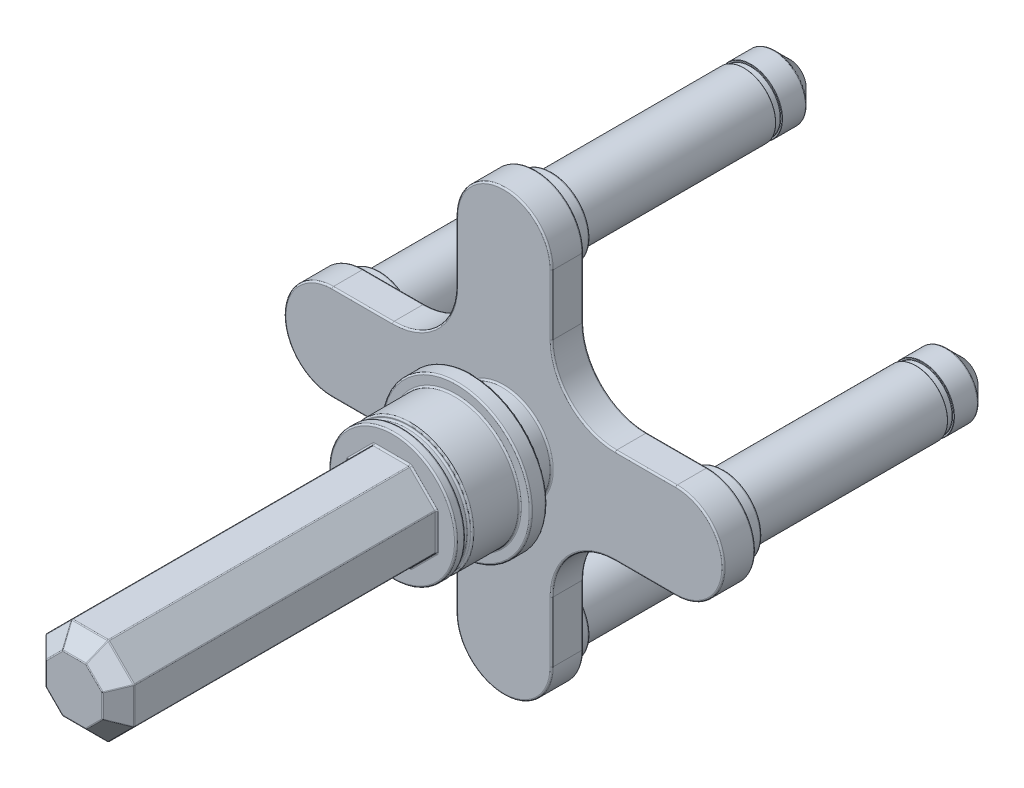
SolidWorks part; units mm, degrees
ref_plane "Front Plane" through (0, 0, 0) normal (0, 0, 1) x (1, 0, 0)
ref_plane "Top Plane" through (0, 0, 0) normal (0, 1, 0) x (1, 0, 0)
ref_plane "Right Plane" through (0, 0, 0) normal (1, 0, 0) x (0, 0, -1)
sketch "Sketch1" plane through (0, 0, 0) normal (0, 0, 1) x (1, 0, 0)
  line L2 (-7.5, 17.5) -> (-7.5, 27)
  line L3 (7.5, 17.5) -> (7.5, 27)
  line L4 (17.5, 7.5) -> (27, 7.5)
  line L5 (17.5, -7.5) -> (27, -7.5)
  line L7 (7.5, -17.5) -> (7.5, -27)
  line L8 (-7.5, -17.5) -> (-7.5, -27)
  line L10 (-17.5, -7.5) -> (-27, -7.5)
  line L11 (-17.5, 7.5) -> (-27, 7.5)
  arc A1 (7.5, 27) -> (-7.5, 27) centre (0, 27) ccw
  circle A2 centre (0, 27) radius 5
  circle A3 centre (27, 0) radius 5
  arc A5 (27, -7.5) -> (27, 7.5) centre (27, 0) ccw
  circle A6 centre (0, -27) radius 5
  arc A8 (-7.5, -27) -> (7.5, -27) centre (0, -27) ccw
  circle A9 centre (-27, 0) radius 5
  arc A11 (-27, 7.5) -> (-27, -7.5) centre (-27, 0) ccw
  arc A12 (7.5, -17.5) -> (17.5, -7.5) centre (17.5, -17.5) cw
  arc A13 (-7.5, -17.5) -> (-17.5, -7.5) centre (-17.5, -17.5) ccw
  arc A14 (7.5, 17.5) -> (17.5, 7.5) centre (17.5, 17.5) ccw
  arc A15 (-7.5, 17.5) -> (-17.5, 7.5) centre (-17.5, 17.5) cw
  point P12 (-13.5, 0)
  point P46 (0, -13.5)
  dimension "D1" = 7.5
  dimension "D2" = 10
  dimension "D4" = 10
  dimension "D5" = 27
extrude "Boss-Extrude1" add sketch "Sketch1" along normal blind 5 contours L2 A15 L11 A11 L10 A13 L8 A8 L7 A12 L5 A5 L4 A14 L3 A1 A2 A3 A6 A9 | A9 | A2 | A3 | A6 region at (0, 0, 0) region at (0, 27, 0) region at (27, 0, 0) region at (0, -27, 0) region at (-27, 0, 0)
sketch "Sketch2" plane through (0, 0, 0) normal (0, 0, -1) x (-1, 0, 0)
  line L0 (7.5, 17.5) -> (7.5, 27) construction
  line L1 (-17.5, -7.5) -> (-27, -7.5) construction
  line L8 (17.5, -7.5) -> (27, -7.5)
  line L9 (7.5, -27) -> (7.5, -17.5)
  line L10 (-7.5, -17.5) -> (-7.5, -27)
  line L11 (-27, -7.5) -> (-17.5, -7.5)
  line L12 (-17.5, 7.5) -> (-27, 7.5)
  line L13 (-7.5, 27) -> (-7.5, 17.5)
  line L14 (7.5, 17.5) -> (7.5, 27)
  line L15 (27, 7.5) -> (17.5, 7.5)
  line L16 (17.5, -7.5) -> (27, -7.5)
  line L17 (7.5, -27) -> (7.5, -17.5)
  line L18 (-7.5, -17.5) -> (-7.5, -27)
  line L19 (-27, -7.5) -> (-17.5, -7.5)
  line L20 (-17.5, 7.5) -> (-27, 7.5)
  line L21 (-7.5, 27) -> (-7.5, 17.5)
  line L22 (7.5, 17.5) -> (7.5, 27)
  line L23 (27, 7.5) -> (17.5, 7.5)
  circle A2 centre (-27, 0) radius 4.975
  circle A4 centre (0, 27) radius 4.975
  circle A6 centre (27, 0) radius 4.975
  circle A8 centre (0, -27) radius 4.975
  arc A16 (17.5, -7.5) -> (7.5, -17.5) centre (17.5, -17.5) ccw
  arc A17 (-7.5, -27) -> (7.5, -27) centre (0, -27) ccw
  arc A18 (-7.5, -17.5) -> (-17.5, -7.5) centre (-17.5, -17.5) ccw
  arc A19 (-27, 7.5) -> (-27, -7.5) centre (-27, 0) ccw
  arc A20 (-17.5, 7.5) -> (-7.5, 17.5) centre (-17.5, 17.5) ccw
  arc A21 (7.5, 27) -> (-7.5, 27) centre (0, 27) ccw
  arc A22 (7.5, 17.5) -> (17.5, 7.5) centre (17.5, 17.5) ccw
  arc A23 (27, -7.5) -> (27, 7.5) centre (27, 0) ccw
  arc A24 (17.5, -7.5) -> (7.5, -17.5) centre (17.5, -17.5) ccw
  arc A25 (-7.5, -27) -> (7.5, -27) centre (0, -27) ccw
  arc A26 (-7.5, -17.5) -> (-17.5, -7.5) centre (-17.5, -17.5) ccw
  arc A27 (-27, 7.5) -> (-27, -7.5) centre (-27, 0) ccw
  arc A28 (-17.5, 7.5) -> (-7.5, 17.5) centre (-17.5, 17.5) ccw
  arc A29 (7.5, 27) -> (-7.5, 27) centre (0, 27) ccw
  arc A30 (7.5, 17.5) -> (17.5, 7.5) centre (17.5, 17.5) ccw
  arc A31 (27, -7.5) -> (27, 7.5) centre (27, 0) ccw
  dimension "D6" = 27
  dimension "D2" = 9.95
  dimension "D1" = 27
  dimension "D3" = 27
  dimension "D4" = 27
  dimension "D7" = 27
  dimension "D8" = 7.5
  dimension "D9" = 7.5
  dimension "D10" = 27
  dimension "D5" = 0
extrude "Boss-Extrude2" add sketch "Sketch2" along normal blind 40 contours A2 | A4 | A6 | A8 region at (27, 0, 0) region at (0, 27, 0) region at (-27, 0, 0) region at (0, -27, 0)
sketch "Sketch3" plane through (0, 0, 5) normal (0, 0, 1) x (1, 0, 0)
  circle A0 centre (0, 0) radius 5 construction
  dimension "D1" = 10
sketch "Sketch4" plane through (0, 0, 0) normal (0, 0, -1) x (-1, 0, 0)
  circle A0 centre (0, 27) radius 4.975 construction
  circle A1 centre (0, 27) radius 4.975
  circle A2 centre (0, 27) radius 6
  dimension "D1" = 12
extrude "Boss-Extrude3" add sketch "Sketch4" along normal blind 2.5
pattern_circular "CirPattern1" count 4 over 360 about axis through (0, 0, 5) along (0, 0, 1) of "Boss-Extrude3"
chamfer "Chamfer1" distance 2.5 angle 45 4 edges at (-31.975, 0, -40) (-4.975, -27, -40) (22.025, 0, -40) (-4.975, 27, -40)
ref_plane "Plane1" through (0, 0, -33.25) normal (0, 0, -1) x (-1, 0, 0)
fillet "Fillet1" radius 0.25 48 edges at (22.25, 7.5, 5) (-7.5, -22.25, 5) (-22.25, 7.5, 5) (-10.4289, 10.4289, 5) (-7.5, 22.25, 5) (27, 4.975, -2.5) (34.5, 0, 0) (27, 6, -2.5) (4.975, -27, -2.5) (0, -34.5, 0) (6, -27, -2.5) (-27, -4.975, -2.5) (-34.5, 0, 0) (-27, -6, -2.5) (-4.975, 27, -2.5) (0, 34.5, 0) (-6, 27, -2.5) (-7.5, 22.25, 0) (-10.4289, 10.4289, 0) (-22.25, 7.5, 0) (-22.25, -7.5, 0) (-10.4289, -10.4289, 0) (-7.5, -22.25, 0) (7.5, -22.25, 0) (10.4289, -10.4289, 0) (22.25, -7.5, 0) (22.25, 7.5, 0) (10.4289, 10.4289, 0) (7.5, 22.25, 0) (-34.5, 0, 5) (-22.25, -7.5, 5) (-10.4289, -10.4289, 5) (0, -34.5, 5) (7.5, -22.25, 5) (10.4289, -10.4289, 5) (22.25, -7.5, 5) (34.5, 0, 5) (10.4289, 10.4289, 5) (7.5, 22.25, 5) (0, 34.5, 5) (-29.475, 0, -40) (-31.975, 0, -37.5) (-2.475, -27, -40) (-4.975, -27, -37.5) (24.525, 0, -40) (22.025, 0, -37.5) (-2.475, 27, -40) (-4.975, 27, -37.5)
sketch "Sketch5" plane through (0, 0, -33.25) normal (0, 0, -1) x (-1, 0, 0)
  circle A0 centre (0, 27) radius 4.7
  circle A1 centre (0, 27) radius 4.975 construction
  circle A2 centre (0, 27) radius 4.975
  dimension "D1" = 9.4
extrude "Cut-Extrude1" cut sketch "Sketch5" against normal mid plane 1
pattern_circular "CirPattern3" count 4 over 360 about axis through (0, 0, 0) along (0, 0, -1) of "Cut-Extrude1"
fillet "Fillet4" radius 0.05 20 edges at (-31.7, 0, -33.75) (-31.7, 0, -32.75) (0, -31.7, -33.75) (0, -31.7, -32.75) (31.7, 0, -33.75) (31.7, 0, -32.75) (0, 31.7, -33.75) (0, 31.7, -32.75) (-31.975, 0, -33.75) (-31.975, 0, -32.75) (0, -31.975, -33.75) (0, -31.975, -32.75) (31.975, 0, -33.75) (31.975, 0, -32.75) (0, 31.975, -33.75) (0, 31.975, -32.75) (33, 0, 0) (6, -27, 0) (-21, 0, 0) (6, 27, 0)
sketch "Sketch6" plane through (0, 0, 0) normal (1, 0, 0) x (0, 0, -1)
  line L0 (-0.25, 0) -> (-100.25, 0) construction
  line L1 (-0.25, 7.5) -> (-0.25, -7.5) construction
  line L2 (-5, 7.5) -> (-12.5, 7.5)
  line L3 (-12.5, 7.5) -> (-12.5, 10)
  line L4 (-12.5, 10) -> (-22.5, 10)
  line L5 (-22.5, 10) -> (-22.5, 7.5)
  line L6 (-22.5, 7.5) -> (-72.5, 7.5)
  line L7 (-72.5, 7.5) -> (-72.5, 0)
  line L8 (-72.5, 0) -> (-5, 0)
  line L9 (-5, 7.25) -> (-5, -7.25) construction
  line L10 (-5, 0) -> (-5, 7.5)
  dimension "D1" = 100
  dimension "D2" = 50
  dimension "D3" = 10
  dimension "D4" = 7.5
  dimension "D5" = 10
  dimension "D6" = 7.5
  dimension "D7" = 10
revolve "Revolve1" add sketch "Sketch6" angle 360 about L0
sketch "Sketch7" plane through (0, 0, 72.5) normal (0, 0, 1) x (1, 0, 0)
  line L15 (-2.8701, -6.9291) -> (2.8701, -6.9291)
  line L16 (2.8701, -6.9291) -> (6.9291, -2.8701)
  line L17 (6.9291, -2.8701) -> (6.9291, 2.8701)
  line L18 (6.9291, 2.8701) -> (2.8701, 6.9291)
  line L19 (2.8701, 6.9291) -> (-2.8701, 6.9291)
  line L20 (-2.8701, 6.9291) -> (-6.9291, 2.8701)
  line L21 (-6.9291, 2.8701) -> (-6.9291, -2.8701)
  line L22 (-6.9291, -2.8701) -> (-2.8701, -6.9291)
  circle A0 centre (0, 0) radius 6.9291 construction
  circle A1 centre (0, 0) radius 7.5
  circle A2 centre (0, 0) radius 7.5
  circle M8 centre (0, 0) radius 7.5
  dimension "D1" = 0
extrude "Cut-Extrude2" cut sketch "Sketch7" against normal up to surface (50 mm away) contours L15 M8 | L16 M8 | L17 M8 | L18 M8 | L19 M8 | L20 M8 | L21 M8 | L22 M8 region at (-5.0616, -5.0616, 72.5) region at (0, -7.1582, 72.5) region at (5.0616, -5.0616, 72.5) region at (-7.1582, 0, 72.5) region at (7.1582, 0, 72.5) region at (-5.0616, 5.0616, 72.5) region at (5.0616, 5.0616, 72.5) region at (0, 7.1582, 72.5) up to face at (-7.5, 0, 22.5)
chamfer "Chamfer2" distance 2.5 angle 45 8 edges at (0, 6.9291, 72.5) (-4.8996, 4.8996, 72.5) (4.8996, 4.8996, 72.5) (6.9291, 0, 72.5) (4.8996, -4.8996, 72.5) (0, -6.9291, 72.5) (-4.8996, -4.8996, 72.5) (-6.9291, 0, 72.5)
ref_plane "Plane2" through (0, 0, 10) normal (0, 0, 1) x (1, 0, 0)
sketch "Sketch9" plane through (0, 0, 10) normal (0, 0, 1) x (1, 0, 0)
  circle A0 centre (0, 0) radius 11.75
  dimension "D1" = 23.5
extrude "Boss-Extrude4" add sketch "Sketch9" along normal up to surface (2.5 mm away) up to face at (-10, 0, 12.5)
fillet "Fillet6" radius 0.25 46 edges at (7.5, 0, 5) (-6.9291, 0, 70) (-4.8996, -4.8996, 70) (0, -6.9291, 70) (4.8996, -4.8996, 70) (6.9291, 0, 70) (4.8996, 4.8996, 70) (0, 6.9291, 70) (-4.8996, 4.8996, 70) (-3.1318, 3.1318, 72.5) (0, 4.4291, 72.5) (3.1318, 3.1318, 72.5) (4.4291, 0, 72.5) (3.1318, -3.1318, 72.5) (0, -4.4291, 72.5) (-3.1318, -3.1318, 72.5) (-4.4291, 0, 72.5) (-10, 0, 12.5) (-10, 0, 22.5) (0, -6.9291, 22.5) (2.8701, -6.9291, 46.25) (-2.8701, -6.9291, 46.25) (6.9291, 0, 22.5) (6.9291, 2.8701, 46.25) (0, 6.9291, 22.5) (-2.8701, 6.9291, 46.25) (-6.9291, 0, 22.5) (-6.9291, -2.8701, 46.25) (4.8996, -4.8996, 22.5) (6.9291, -2.8701, 46.25) (4.8996, 4.8996, 22.5) (2.8701, 6.9291, 46.25) (-4.8996, 4.8996, 22.5) (-6.9291, 2.8701, 46.25) (-4.8996, -4.8996, 22.5) (5.6791, -2.3524, 71.25) (2.3524, -5.6791, 71.25) (5.6791, 2.3524, 71.25) (-2.3524, -5.6791, 71.25) (2.3524, 5.6791, 71.25) (-5.6791, -2.3524, 71.25) (-2.3524, 5.6791, 71.25) (-5.6791, 2.3524, 71.25) (7.5, 0, 10) (-11.75, 0, 12.5) (11.75, 0, 10)
ref_plane "Plane3" through (0, 0, 20.5) normal (0, 0, 1) x (1, 0, 0)
sketch "Sketch10" plane through (0, 0, 20.5) normal (0, 0, 1) x (1, 0, 0)
  circle A0 centre (0, 0) radius 9.4
  circle A1 centre (0, 0) radius 10 construction
  circle A2 centre (0, 0) radius 10
  dimension "D1" = 18.8
extrude "Cut-Extrude3" cut sketch "Sketch10" against normal mid plane 1.1 contours A2 | A0
fillet "Fillet7" radius 0.25 4 edges at (10, 0, 19.95) (10, 0, 21.05) (9.4, 0, 19.95) (9.4, 0, 21.05)
